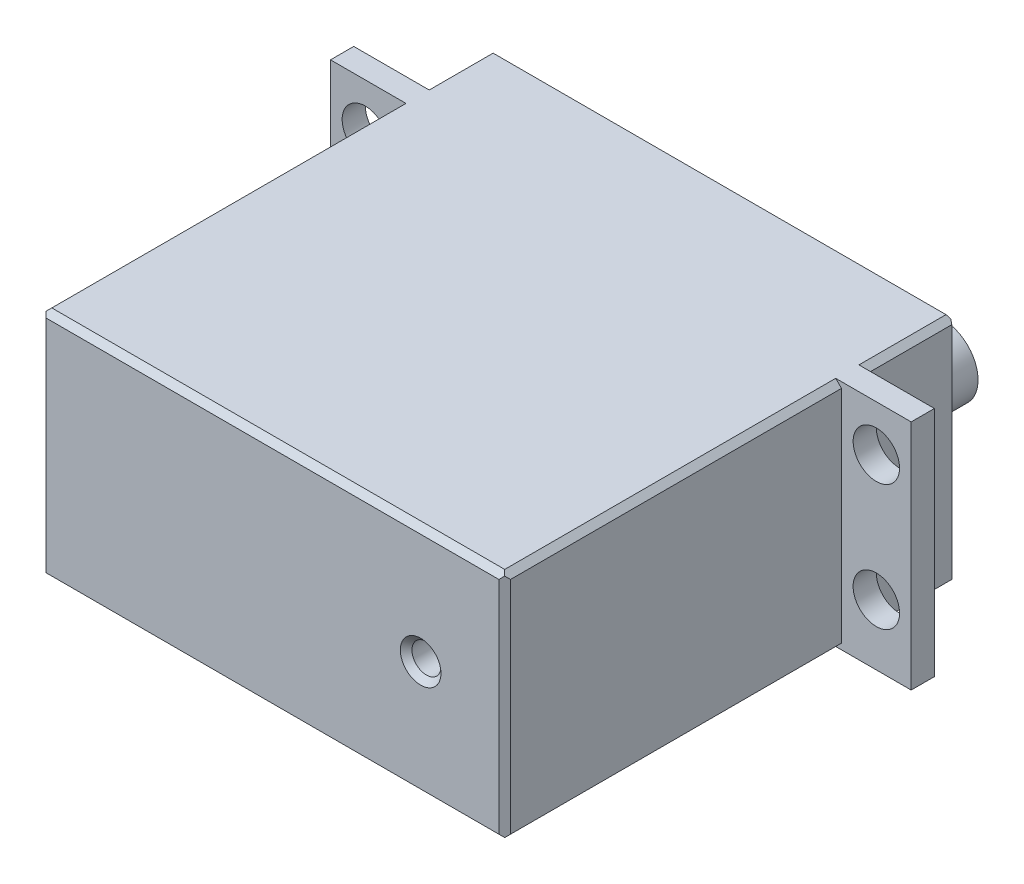
SolidWorks part; units mm, degrees
ref_plane "前视基准面" through (0, 0, 0) normal (0, 0, 1) x (1, 0, 0)
ref_plane "上视基准面" through (0, 0, 0) normal (0, 1, 0) x (1, 0, 0)
ref_plane "右视基准面" through (0, 0, 0) normal (1, 0, 0) x (0, 0, -1)
sketch "草图1" plane through (0, 0, 0) normal (0, 0, 1) x (1, 0, 0)
  line L1 (-20, 10) -> (20, 10)
  line L2 (-20, 10) -> (-20, -10)
  line L3 (-20, -10) -> (20, -10)
  line L4 (20, 10) -> (20, -10)
  line L5 (-20, 10) -> (20, -10) construction
  line L6 (-20, -10) -> (20, 10) construction
  point P0 (0, 0)
extrude "凸台-拉伸1" add sketch "草图1" along normal blind 39
sketch "草图2" plane through (-20, 0, 0) normal (-1, 0, 0) x (0, 0, 1)
  line L0 (8, 10) -> (8, -10)
  line L1 (39, 10) -> (0, 10) construction
  line L2 (39, -10) -> (0, -10) construction
  line L3 (0, 10) -> (0, -10) construction
  dimension "D1" = 8
sketch "草图3" plane through (20, 0, 0) normal (1, 0, 0) x (0, 0, -1)
  line L0 (-8, 10) -> (-8, -10)
  line L1 (-9.9592, 10) -> (-9.9592, -10)
  line L2 (-39, 10) -> (0, 10) construction
  line L3 (-39, -10) -> (0, -10) construction
extrude "拉伸-薄壁1" add sketch "草图3" along normal blind 6 thin contours L0 thin type one direction wall 2
extrude "拉伸-薄壁2" add sketch "草图2" along normal blind 6 thin contours L0 thin type one direction wall 2
sketch "草图5" plane through (0, 0, 8) normal (0, 0, -1) x (-1, 0, 0)
  circle A0 centre (-23, 6.0528) radius 1.9967
  circle A1 centre (-23, -4.7658) radius 2
sketch "草图6" plane through (0, 0, 6) normal (0, 0, -1) x (-1, 0, 0)
  circle A0 centre (23, 6.0528) radius 2
  circle A1 centre (23, -4.7658) radius 2
extrude "切除-拉伸6" cut sketch "草图5" against normal blind 2
extrude "切除-拉伸7" cut sketch "草图6" against normal blind 2
sketch "草图10" plane through (0, 0, 0) normal (0, 0, -1) x (-1, 0, 0)
  line L0 (-26, 10) -> (-26, -10) construction
  circle A0 centre (-12.7625, 0) radius 2.9978
  dimension "D1" = 20
extrude "凸台-拉伸2" add sketch "草图10" along normal blind 6 contours A0
sketch "草图11" plane through (0, 0, 0) normal (0, 0, -1) x (-1, 0, 0)
  circle A0 centre (-12.7625, 0) radius 5.5764
extrude "凸台-拉伸3" add sketch "草图11" along normal blind 1
sketch "草图12" plane through (0, 0, 0) normal (0, 0, -1) x (-1, 0, 0)
  circle A0 centre (-12.7625, 0) radius 4.8827
extrude "凸台-拉伸4" add sketch "草图12" along normal blind 1.5
hole_wizard "M3 螺纹孔2" positions "3D草图2" profile "草图14" tap size "M3" standard "GB" end condition up to next
sketch3d "3D草图2"
  line L0 (12.7625, 0, -1.5) -> (12.7625, 0, -1) construction
  line L1 (12.7625, 0, -1) -> (12.7625, 0, 0) construction
  line L2 (12.7625, 0, -6) -> (12.7625, 0, -1.5) construction
  point P0 (12.7625, 0, -1)
  point P6 (12.7625, 0, -6)
sketch "草图14" plane through (12.7625, 0, -6) normal (1, 0, 0) x (0, 1, 0)
  line L0 (0, 0) -> (0, 45.001)
  line L1 (0, 45.001) -> (1.25, 45.001)
  line L2 (1.25, 45.001) -> (1.25, 0.275)
  line L3 (1.25, 0.275) -> (1.525, 0)
  line L5 (1.525, 0) -> (0, 0)
  line L6 (-1.25, 0.275) -> (-1.525, 0) construction
  line L11 (0, -6.35) -> (0, 107.95) construction
  dimension "通孔螺纹孔钻头直径" = 2.5
  dimension "通孔螺纹孔钻头深度" = 45.001
  dimension "近端锥形沉头孔直径" = 3.05
  dimension "近端锥形沉头孔角度" = 90
cosmetic thread "孔螺纹线4" parameters "D2"=3
chamfer "倒角5" distance 0.5 angle 45 5 edges at (0, 10, 0) (-20, 0, 0) (0, -10, 0) (20, 0, 0) (18.3388, 0, 0)
chamfer "倒角6" distance 0.5 angle 45 5 edges at (0, -10, 39) (-20, 0, 39) (0, 10, 39) (20, 0, 39) (14.0125, 0, 39)
chamfer "倒角7" distance 0.5 angle 45 8 edges at (-20, 10, 3.25) (-20, 10, 23.25) (20, 10, 24.25) (20, 10, 4.25) (-20, -10, 3.25) (-20, -10, 23.25) (20, -10, 4.25) (20, -10, 24.25)
ref_plane "基准面1" through (19.5, 9.5, 0) normal (0, -1, 0) x (-1, 0, 0)
fillet "圆角1" radius 3 4 edges at (0, -9.5, 0) (19.5, 0, 0) (0, 9.5, 0) (-19.5, 0, 0)
